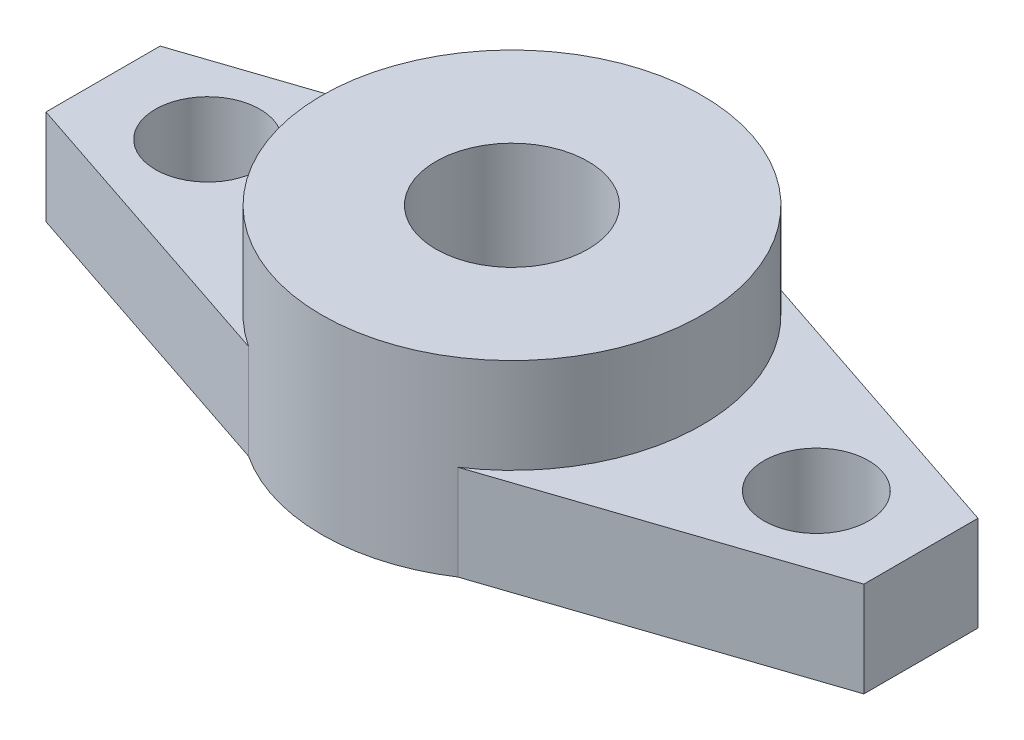
SolidWorks part; units mm, degrees
ref_plane "Front Plane" through (0, 0, 0) normal (0, 0, 1) x (1, 0, 0)
ref_plane "Top Plane" through (0, 0, 0) normal (0, 1, 0) x (1, 0, 0)
ref_plane "Right Plane" through (0, 0, 0) normal (1, 0, 0) x (0, 0, -1)
sketch "Sketch1" plane through (0, 0, 0) normal (0, 1, 0) x (1, 0, 0)
  line L0 (-16, 0) -> (16, 0) construction
  line L1 (21.5, 10) -> (-21.5, 10)
  line L2 (21.5, 10) -> (21.5, -10)
  line L3 (21.5, -10) -> (-21.5, -10)
  line L4 (-21.5, 10) -> (-21.5, -10)
  line L5 (21.5, 10) -> (-21.5, -10) construction
  line L6 (21.5, -10) -> (-21.5, 10) construction
  line L7 (-21.5, 3) -> (-5.5, 8.3516)
  line L8 (-21.5, -3) -> (-5.5, -8.3516)
  line L9 (0, 10) -> (0, -10) construction
  line L10 (21.5, -3) -> (5.5, -8.3516)
  line L11 (21.5, 3) -> (5.5, 8.3516)
  circle A0 centre (-16, 0) radius 2.75
  circle A1 centre (16, 0) radius 2.75
  circle A2 centre (0, 0) radius 10
  point P0 (0, 0)
  dimension "D4" = 5.5
  dimension "D5" = 20
  dimension "D1" = 43
  dimension "D2" = 20
  dimension "D3" = 32
  dimension "D6" = 7
  dimension "D7" = 16
extrude "Boss-Extrude1" add sketch "Sketch1" along normal blind 5 contours A2 L10 L2 L11 A1 | A2 L7 L4 L8 A0 region at (21.2687, 0, 0) region at (-10.2313, 0, 0)
extrude "Boss-Extrude2" add sketch "Sketch1<3>" along normal blind 10 contours A2 region at (0, 0, 0)
sketch "Sketch1<3>" plane through (0, 0, 0) normal (0, 1, 0) x (1, 0, 0) same geometry as "Sketch1"
sketch "Sketch2" plane through (0, 10, 0) normal (0, 1, 0) x (1, 0, 0)
  circle A0 centre (0, 0) radius 4
  dimension "D1" = 8
extrude "Cut-Extrude1" cut sketch "Sketch2" against normal through all
